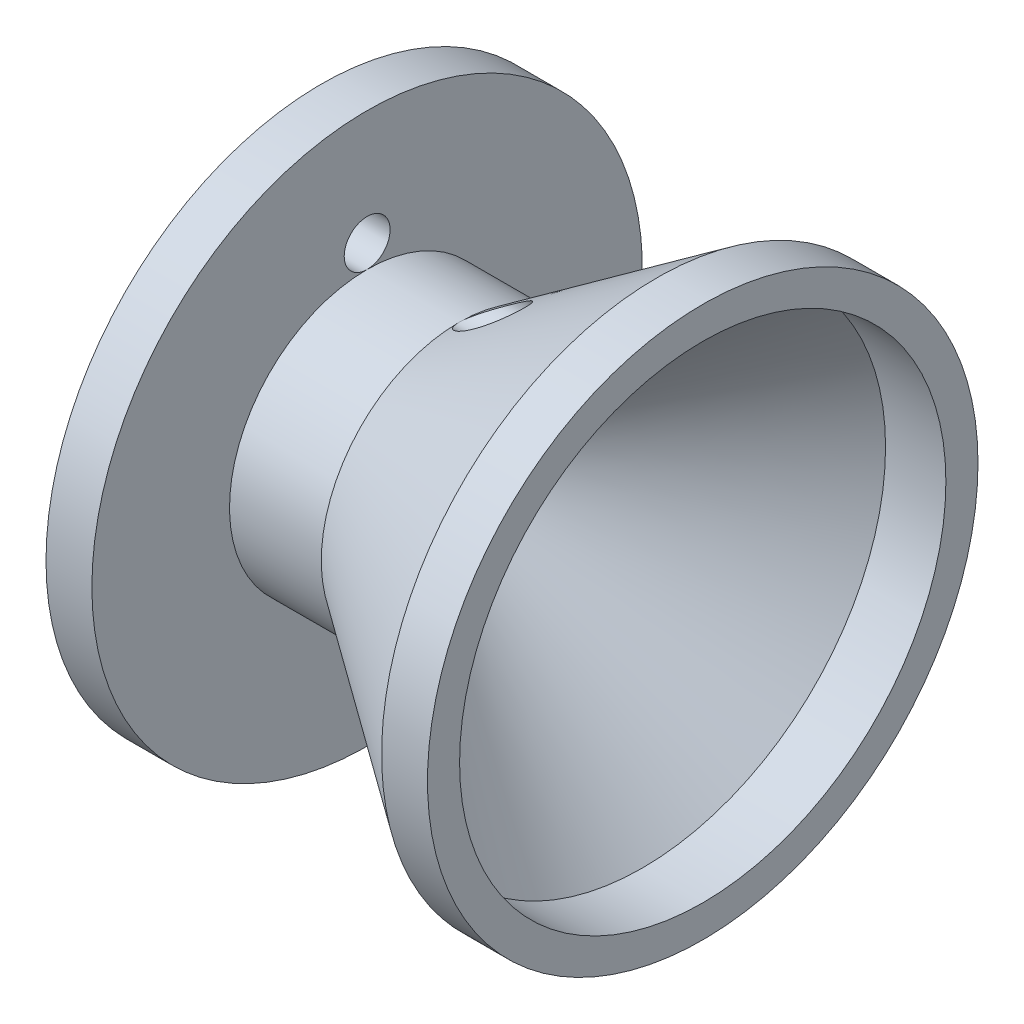
SolidWorks part; units mm, degrees
ref_plane "前视基准面" through (0, 0, 0) normal (0, 0, 1) x (1, 0, 0)
ref_plane "上视基准面" through (0, 0, 0) normal (0, 1, 0) x (1, 0, 0)
ref_plane "右视基准面" through (0, 0, 0) normal (1, 0, 0) x (0, 0, -1)
other "Configuration Table"
sketch "草图1" plane through (0, 0, 0) normal (1, 0, 0) x (0, 0, -1)
  circle A0 centre (-12, 12) radius 6
  dimension "D3" = 12
extrude "凸台-拉伸1" add sketch "草图1" along normal blind 10
sketch "草图7" plane through (10, 0, 0) normal (1, 0, 0) x (0, 0, -1)
  circle A0 centre (-12, 12) radius 12
  dimension "D1" = 24
extrude "凸台-拉伸2" add sketch "草图7" along normal blind 2
sketch "草图8" plane through (0, 0, 0) normal (-1, 0, 0) x (0, 0, 1)
  circle A0 centre (12, 12) radius 12
  dimension "D1" = 24
extrude "凸台-拉伸3" add sketch "草图8" along normal blind 2
sketch "草图9" plane through (-2, 0, 0) normal (-1, 0, 0) x (0, 0, 1)
  circle A0 centre (12, 12) radius 2.6
  dimension "D1" = 5.2
extrude "切除-拉伸4" cut sketch "草图9" against normal blind 22
fillet "圆角3" radius 0.4 1 edges at (-2, 12, 14.6)
sketch "草图10" plane through (-2, 0, 0) normal (-1, 0, 0) x (0, 0, 1)
  line L0 (12, 12) -> (12, 19) construction
  circle A0 centre (12, 19) radius 1
  dimension "D2" = 2
  dimension "D1" = 7
extrude "切除-拉伸5" cut sketch "草图10" against normal blind 50
chamfer "倒角1" distance 6 angle 45 1 edges at (10, 12, 6)
chamfer "倒角2" distance 8 angle 45 1 edges at (12, 12, 9.4)
sketch "草图15" plane through (12, 0, 0) normal (1, 0, 0) x (0, 0, -1)
  circle A0 centre (-12, 12) radius 10.6
  circle A1 centre (-12, 12) radius 12
  circle A2 centre (-12, 12) radius 12
  dimension "D1" = 0
extrude "凸台-拉伸5" add sketch "草图15" along normal blind 2.63
ref_plane "基准面1" through (0, 0, 12) normal (0, 0, 1) x (1, 0, 0)
sketch "草图18" plane through (0, 0, 12) normal (0, 0, 1) x (1, 0, 0)
  line L0 (14.63, 24) -> (12.63, 24)
  line L1 (14.63, 24) -> (10, 24) construction
  line L2 (12.63, 24) -> (4, 18)
  line L3 (4, 18) -> (4, 24)
  line L4 (4, 24) -> (12.63, 24)
  dimension "D1" = 2
revolve "切除-旋转1" cut sketch "草图18" angle 360 about axis through (10, 12, 12) along (-1, 0, 0)
